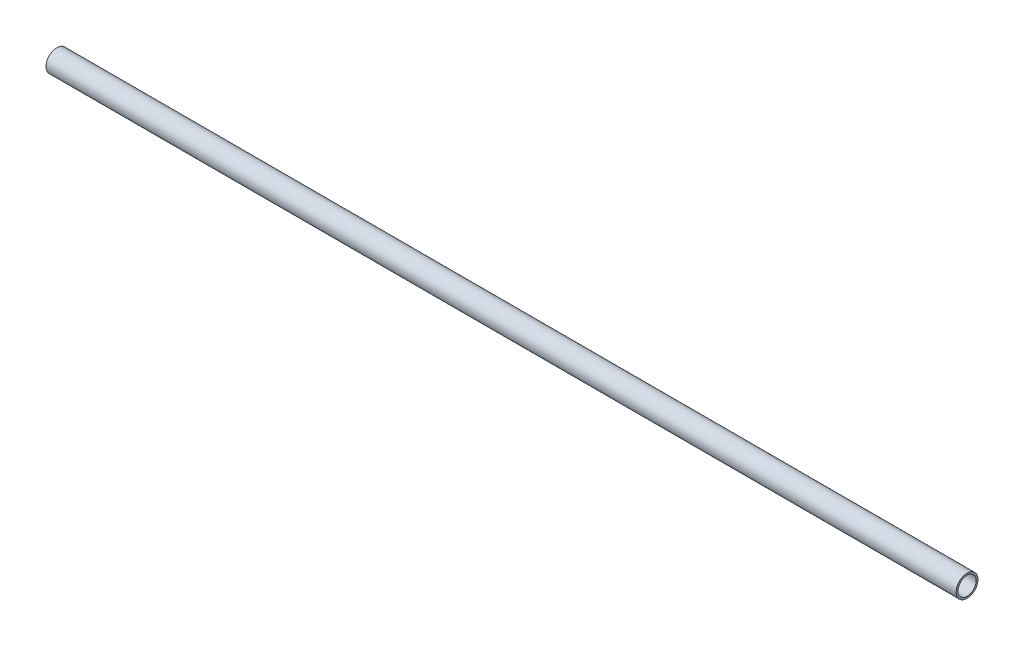
SolidWorks part; units mm, degrees
ref_plane "Front Plane" through (0, 0, 0) normal (1, 0, 0) x (0, 1, 0)
ref_plane "Top Plane" through (0, 0, 0) normal (0, 0, 1) x (0, 1, 0)
ref_plane "Right Plane" through (0, 0, 0) normal (0, 1, 0) x (-1, 0, 0)
sketch "Sketch1" plane through (0, 0, 0) normal (1, 0, 0) x (0, 1, 0)
  circle A0 centre (0, 0) radius 6
  circle A1 centre (0, 0) radius 5
  dimension "D1" = 12
  dimension "D2" = 10
extrude "Boss-Extrude1" add sketch "Sketch1" along normal blind 500
